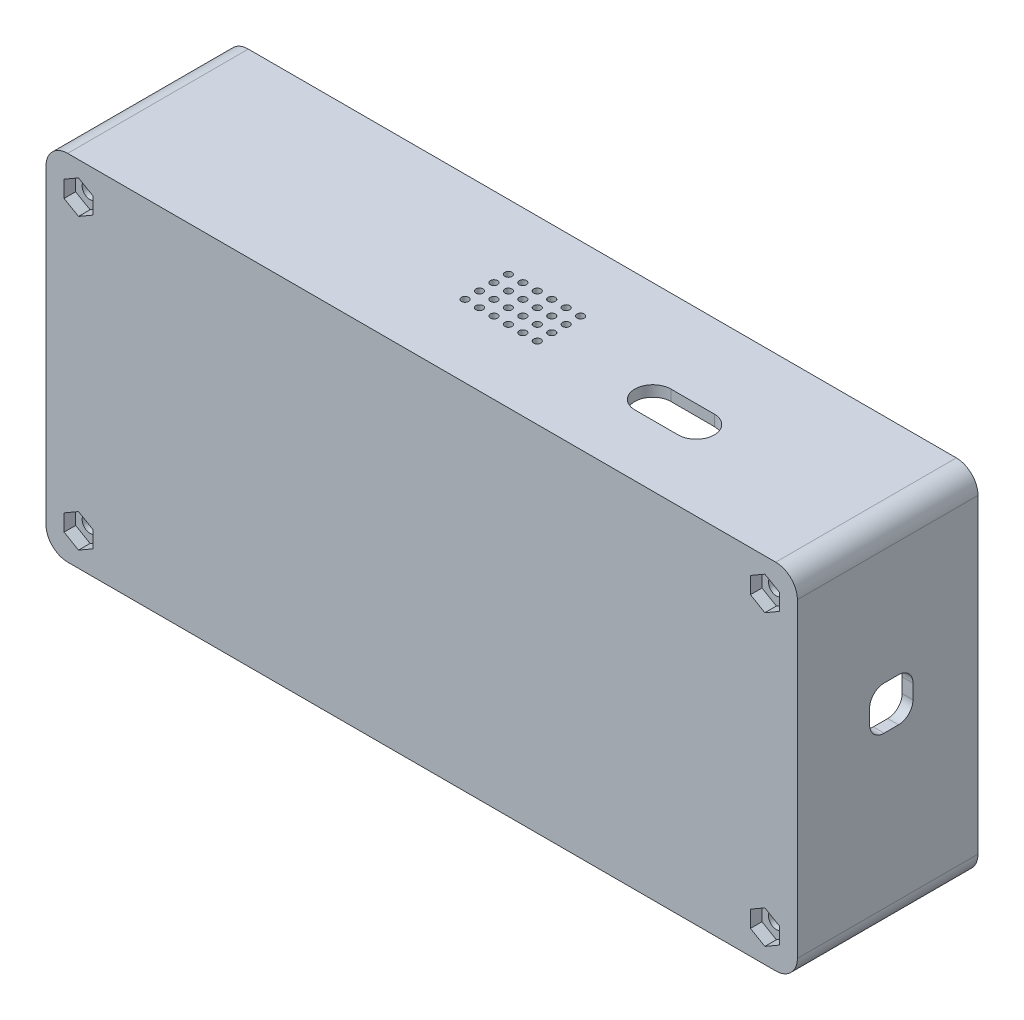
SolidWorks part; units mm, degrees
ref_plane "前视基准面" through (0, 0, 0) normal (0, 0, 1) x (1, 0, 0)
ref_plane "上视基准面" through (0, 0, 0) normal (0, 1, 0) x (1, 0, 0)
ref_plane "右视基准面" through (0, 0, 0) normal (1, 0, 0) x (0, 0, -1)
sketch "草图1" plane through (0, 0, 0) normal (0, 0, 1) x (1, 0, 0)
  line L0 (-52, 24.5) -> (52, 24.5)
  line L1 (-50, 22.5) -> (50, 22.5) construction
  line L2 (-50, 22.5) -> (-50, -22.5) construction
  line L3 (-50, -22.5) -> (50, -22.5) construction
  line L4 (50, 22.5) -> (50, -22.5) construction
  line L5 (-50, 22.5) -> (50, -22.5) construction
  line L6 (-50, -22.5) -> (50, 22.5) construction
  line L7 (52, 24.5) -> (52, -24.5)
  line L8 (-52, -24.5) -> (52, -24.5)
  line L9 (-52, 24.5) -> (-52, -24.5)
  circle A0 centre (-47.5, 20) radius 1.1
  circle A1 centre (47.5, 20) radius 1.1
  circle A2 centre (47.5, -20) radius 1.1
  circle A3 centre (-47.5, -20) radius 1.1
  point P0 (0, 0)
  dimension "D5" = 2.2
  dimension "D6" = 2.2
  dimension "D9" = 2.2
  dimension "D12" = 2.5
  dimension "D13" = 2.5
  dimension "D1" = 100
  dimension "D2" = 45
  dimension "D3" = 2.5
  dimension "D4" = 2.5
  dimension "D7" = 2.5
  dimension "D8" = 2.5
  dimension "D10" = 2.5
  dimension "D11" = 2.5
  dimension "D15" = 2
  dimension "D14" = 2
extrude "凸台-拉伸1" add sketch "草图1" along normal blind 25
fillet "圆角1" radius 3 4 edges at (52, -24.5, 12.5) (-52, -24.5, 12.5) (-52, 24.5, 12.5) (52, 24.5, 12.5)
sketch "草图2" plane through (0, 0, 25) normal (0, 0, 1) x (1, 0, 0)
  line L0 (0, 0) -> (52, 0) construction
  line L1 (-45.5, 18.8453) -> (-45.5, 21.1547)
  line L2 (-45.5, 21.1547) -> (-47.5, 22.3094)
  line L3 (-47.5, 22.3094) -> (-49.5, 21.1547)
  line L4 (-49.5, 21.1547) -> (-49.5, 18.8453)
  line L5 (-49.5, 18.8453) -> (-47.5, 17.6906)
  line L6 (-47.5, 17.6906) -> (-45.5, 18.8453)
  line L7 (52, -21.5) -> (52, 21.5) construction
  line L8 (-45.5, -18.8453) -> (-45.5, -21.1547)
  line L9 (-45.5, -21.1547) -> (-47.5, -22.3094)
  line L10 (-47.5, -22.3094) -> (-49.5, -21.1547)
  line L11 (-49.5, -21.1547) -> (-49.5, -18.8453)
  line L12 (-49.5, -18.8453) -> (-47.5, -17.6906)
  line L13 (-47.5, -17.6906) -> (-45.5, -18.8453)
  line L14 (0, 0) -> (0, -24.5) construction
  line L15 (-49, -24.5) -> (49, -24.5) construction
  line L16 (49.5, 21.1547) -> (49.5, 18.8453)
  line L17 (45.5, 21.1547) -> (47.5, 22.3094)
  line L18 (47.5, 22.3094) -> (49.5, 21.1547)
  line L19 (49.5, 18.8453) -> (47.5, 17.6906)
  line L20 (47.5, 17.6906) -> (45.5, 18.8453)
  line L21 (45.5, 18.8453) -> (45.5, 21.1547)
  line L22 (49.5, -18.8453) -> (47.5, -17.6906)
  line L23 (49.5, -21.1547) -> (49.5, -18.8453)
  line L24 (47.5, -22.3094) -> (49.5, -21.1547)
  line L25 (45.5, -21.1547) -> (47.5, -22.3094)
  line L26 (47.5, -17.6906) -> (45.5, -18.8453)
  line L27 (45.5, -18.8453) -> (45.5, -21.1547)
  circle A0 centre (-47.5, 20) radius 2 construction
  circle A1 centre (-47.5, 20) radius 1.1 construction
  dimension "D1" = 4
extrude "切除-拉伸1" cut sketch "草图2" against normal blind 1.6
shell "抽壳2" thickness 1.5 removed face at (0, 0, 0)
sketch "草图3" plane through (0, 0, 0) normal (0, 0, -1) x (-1, 0, 0)
  line L1 (0, 55) -> (0, -55) construction
  line L2 (55, 0) -> (-55, 0) construction
  circle A0 centre (-47.5, 20) radius 1.1 construction
  circle A1 centre (-47.5, 20) radius 1.1
  circle A2 centre (-47.5, 20) radius 2.6 construction
  circle A3 centre (-47.5, 20) radius 2.6
  circle A4 centre (47.5, 20) radius 1.1
  circle A5 centre (47.5, 20) radius 2.6
  circle A6 centre (47.5, -20) radius 1.1
  circle A7 centre (47.5, -20) radius 2.6
  circle A8 centre (-47.5, -20) radius 1.1
  circle A9 centre (-47.5, -20) radius 2.6
extrude "切除-拉伸2" cut sketch "草图3" against normal blind 17
sketch "草图5" plane through (0, 24.5, 0) normal (0, 1, 0) x (1, 0, 0)
  line L0 (-52, -14) -> (52, -14) construction
  line L1 (-52, -25) -> (-52, 0) construction
  line L2 (52, 0) -> (52, -25) construction
  line L3 (49, -25) -> (-49, -25) construction
  line L4 (-45.5, -25) -> (-45.5, 0) construction
  line L5 (49, 0) -> (-49, 0) construction
  line L6 (45.5, 0) -> (45.5, -25) construction
  line L9 (21, -14) -> (27, -14) construction
  line L10 (21, -11.5) -> (27, -11.5)
  line L11 (21, -16.5) -> (27, -16.5)
  arc A2 (21, -11.5) -> (21, -16.5) centre (21, -14) ccw
  arc A3 (27, -16.5) -> (27, -11.5) centre (27, -14) ccw
  point P16 (24, -14)
  point P21 (29.5, -14)
  point P22 (18.5, -14)
  dimension "D1" = 11
  dimension "D2" = 6.5
  dimension "D3" = 6.5
  dimension "D4" = 16
  dimension "D5" = 11
  dimension "D6" = 5
extrude "切除-拉伸3" cut sketch "草图5" against normal blind 17
sketch "草图6" plane through (52, 0, 0) normal (1, 0, 0) x (0, 0, -1)
  line L0 (-12, 21.5) -> (-12, -21.5) construction
  line L1 (0, 21.5) -> (-25, 21.5) construction
  line L2 (-25, -21.5) -> (0, -21.5) construction
  line L3 (-25, -21.5) -> (-25, 21.5) construction
  line L4 (-25, 2.5) -> (0, 2.5) construction
  line L5 (0, -21.5) -> (0, 21.5) construction
  line L6 (-25, 24.5) -> (0, 24.5) construction
  line L8 (-15, 5.5) -> (-9, 5.5)
  line L9 (-15, 5.5) -> (-15, -0.5)
  line L10 (-15, -0.5) -> (-9, -0.5)
  line L11 (-9, 5.5) -> (-9, -0.5)
  line L12 (-15, 5.5) -> (-9, -0.5) construction
  line L13 (-15, -0.5) -> (-9, 5.5) construction
  point P14 (-12, 2.5)
  point P17 (-12, 2.5)
  dimension "D1" = 13
  dimension "D2" = 22
  dimension "D3" = 6
extrude "切除-拉伸4" cut sketch "草图6" against normal through all both and the other way through all
sketch "草图7" plane through (0, -24.5, 0) normal (0, -1, 0) x (1, 0, 0)
  line L0 (-35, 0) -> (-35, 25) construction
  line L1 (-49, 0) -> (49, 0) construction
  line L2 (-49, 25) -> (49, 25) construction
  line L3 (-52, 0) -> (-52, 25) construction
  line L4 (-20, 0) -> (-20, 25) construction
  line L5 (-49, 15) -> (49, 15) construction
  line L6 (-49, 25) -> (-49, 0) construction
  line L7 (49, 0) -> (49, 25) construction
  line L9 (-35, 11) -> (-20, 11)
  line L10 (-35, 11) -> (-35, 18)
  line L11 (-35, 18) -> (-20, 18)
  line L12 (-20, 11) -> (-20, 18)
  dimension "D1" = 17
  dimension "D2" = 15
  dimension "D3" = 10
  dimension "D4" = 7
  dimension "D5" = 7
extrude "切除-拉伸5" cut sketch "草图7" against normal blind 17
sketch "草图8" plane through (0, 24.5, 0) normal (0, 1, 0) x (1, 0, 0)
  line L0 (-49, -7) -> (49, -7) construction
  line L1 (-49, 0) -> (-49, -25) construction
  line L2 (49, -25) -> (49, 0) construction
  line L3 (49, 0) -> (-49, 0) construction
  line L4 (0, 0) -> (0, -25) construction
  line L5 (49, -25) -> (-49, -25) construction
  line L7 (-30, -7) -> (-20, -7)
  line L8 (-30, -7) -> (-30, -9)
  line L9 (-30, -9) -> (-20, -9)
  line L10 (-20, -7) -> (-20, -9)
  point P16 (-20, -8)
  dimension "D1" = 7
  dimension "D2" = 2
  dimension "D3" = 10
  dimension "D4" = 20
extrude "凸台-拉伸2" add sketch "草图8" against normal blind 3
mirror "镜向1" about plane through (0, 0, 0) normal (0, 1, 0) of "凸台-拉伸2"
fillet "圆角3" radius 2 4 edges at (51.25, -0.5, 15) (51.25, 5.5, 9) (51.25, -0.5, 9) (51.25, 5.5, 15)
fillet "圆角4" radius 2 4 edges at (-51.25, -0.5, 9) (-51.25, 5.5, 9) (-51.25, -0.5, 15) (-51.25, 5.5, 15)
sketch "草图10" plane through (0, -24.5, 0) normal (0, -1, 0) x (1, 0, 0)
  line L0 (-49, 25) -> (49, 25) construction
  line L1 (52, 25) -> (52, 0) construction
  circle A0 centre (-4, 9) radius 0.5
  dimension "D1" = 1
  dimension "D3" = 56
  dimension "D2" = 16
extrude "切除-拉伸6" cut sketch "草图10" against normal through all both and the other way through all
pattern_linear "阵列(线性)1" count 4 spacing 2 along (0, 0, 1) count 6 spacing 2 along (1, 0, 0) of "切除-拉伸6"
